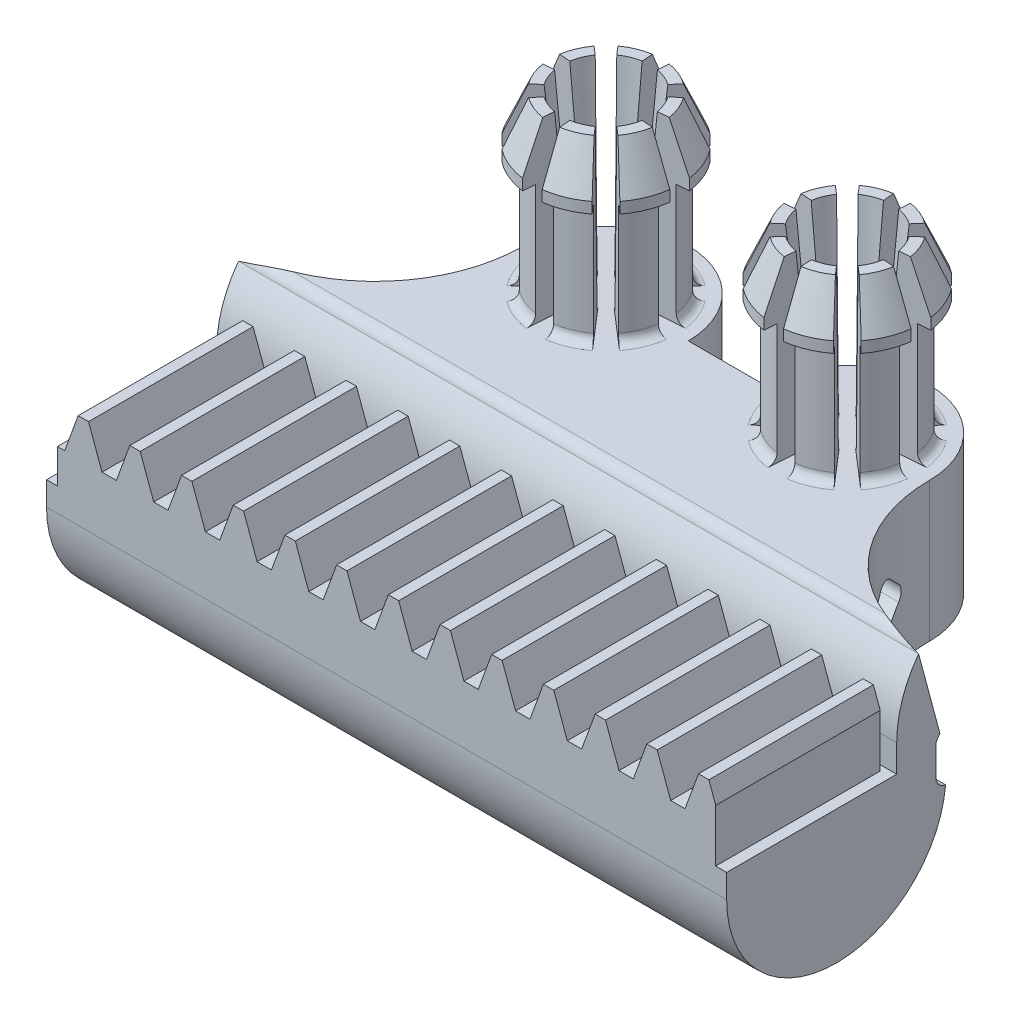
SolidWorks part; units mm, degrees
extrude "Blank" add sketch "BlankSke" against normal blind 10
sketch "BlankSke" plane through (0, 0, 0) normal (0, 0, 1) x (1, 0, 0)
  line L1 (0, 0) -> (60, 0)
  line L2 (0, 0) -> (0, 6.5)
  line L3 (0, 6.5) -> (60, 6.5)
  line L4 (60, 0) -> (60, 6.5)
  dimension "Length" = 60
ref_plane "Plane1" through (0, 0, 0) normal (0, 0, 1) x (1, 0, 0)
ref_plane "Plane2" through (0, 0, 0) normal (0, 1, 0) x (1, 0, 0)
ref_plane "Plane3" through (0, 0, 0) normal (1, 0, 0) x (0, 0, -1)
other "Configuration Table"
sketch "HoldingSke" plane through (0, 0, 0) normal (0, 1, 0) x (1, 0, 0)
  line L0 (0, 0) -> (0.0928, 0.6602)
  line L1 (-15, 0) -> (100, 0) construction
  line L2 (0, 0) -> (-2.1039, 2.3779)
  line L3 (0, 0) -> (-11.863, 4.5341)
  line L4 (0, 0) -> (8.3795, 2.0892)
  line L5 (0, 0) -> (-23.7986, -8.8762)
  line L6 (0, 0) -> (-10.5278, -7.1032)
  line L9 (-71.009, 38.7566) -> (-14.6274, 59.2778)
  line L10 (-76.2, 3.8779) -> (-71.2, 3.8779)
  line L11 (0, 0) -> (-10, 0)
  line L12 (-76.2, 101.6) -> (-76.147, 101.6)
  line L13 (24.9733, 27.94) -> (52.9518, 28.4284)
  line L14 (24.9733, 27.94) -> (24.9743, 27.94)
  line L15 (24.9733, 27.94) -> (100.4006, 29.5858)
  circle A0 centre (0, 0) radius 19.05
  circle A1 centre (0, 0) radius 2.5
  circle A2 centre (0, 0) radius 12.7
  dimension "Num_teeth" = 14
  dimension "Width" = 10
  dimension "Length" = 60
  dimension "Pitch_height" = 5
sketch "TooCutSkeIll" plane through (0, 0, 0) normal (0, 0, 1) x (1, 0, 0)
  line L0 (-1.8687, 6.4605) -> (-0.7447, 3.3724)
  line L1 (-0.3914, 3.125) -> (0.3914, 3.125)
  line L2 (0.7447, 3.3724) -> (1.8687, 6.4605)
  line L3 (60, 6.5) -> (0, 6.5) construction
  line L4 (0, 0) -> (0, 64.897) construction
  line L5 (-13.208, 5) -> (12.954, 5) construction
  line L6 (0, 0) -> (60, 0) construction
  line L7 (1.3371, 5) -> (1.3371, 48.7463) construction
  line L8 (-1.3371, 5) -> (-1.3371, 48.7463) construction
  line L9 (1.9251, 6.5) -> (1.9251, 6.5254)
  line L10 (-1.9251, 6.5) -> (-1.9251, 6.5254)
  line L11 (-1.9251, 6.5254) -> (1.9251, 6.5254)
  arc A0 (0.3914, 3.125) -> (0.7447, 3.3724) centre (0.3914, 3.501) ccw
  arc A1 (-0.7447, 3.3724) -> (-0.3914, 3.125) centre (-0.3914, 3.501) ccw
  arc A2 (1.9251, 6.5) -> (1.8687, 6.4605) centre (1.9251, 6.44) ccw
  arc A3 (-1.8687, 6.4605) -> (-1.9251, 6.5) centre (-1.9251, 6.44) ccw
  dimension "Addendum_plus" = 1.5254
  dimension "Pitch_height" = 5
  dimension "Pressure_angle" = 20
  dimension "Gap_width" = 2.6742
  dimension "Dedendum" = 1.875
extrude "ToothCutIll" [suppressed] cut sketch "TooCutSkeIll" against normal through all
sketch "TooCutSkeSim" plane through (0, 0, 0) normal (0, 0, 1) x (1, 0, 0)
  line L0 (0.6547, 3.125) -> (-0.6547, 3.125)
  line L1 (1.8923, 6.5254) -> (0.6547, 3.125)
  line L2 (0, 17.4625) -> (0, 53.467) construction
  line L3 (1.8923, 6.5254) -> (-1.8923, 6.5254)
  line L6 (-1.8923, 6.5254) -> (-0.6547, 3.125)
  line L9 (-1.3371, 5) -> (1.3371, 5) construction
  line L10 (0, 0) -> (60, 0) construction
  line L11 (1.3371, 5) -> (1.3371, 53.467) construction
  line L12 (-1.3371, 5) -> (-1.3371, 53.467) construction
  dimension "Addendum_plus" = 1.5254
  dimension "Pitch_height" = 5
  dimension "Pressure_angle" = 20
  dimension "Gap_width" = 2.6742
  dimension "Dedendum" = 1.875
extrude "ToothCutSim" cut sketch "TooCutSkeSim" against normal through all
pattern_linear "TeethCuts" count 14 spacing 4.7124 along (1, 0, 0) of "ToothCutIll", "ToothCutSim"
sketch "Sketch1" plane through (60, 0, 0) normal (1, 0, 0) x (0, 0, -1)
  line L0 (0, 0) -> (0, -10.8205)
  line L2 (10.5, 0) -> (10.5, 8.5)
  line L4 (10, 6.5) -> (0, 6.5) construction
  line L5 (10, 0) -> (10, 4.7911) construction
  line L6 (10.5, 8.5) -> (12.5, 8.5)
  line L7 (12.5, 8.5) -> (14.6603, 0.4239)
  line L8 (10.5, 0) -> (0, 0)
  arc A0 (0, -10.8205) -> (14.6603, 0.4239) centre (5, -2.1603) ccw
  dimension "D1" = 20
  dimension "D2" = 2
  dimension "D3" = 0.5
  dimension "D4" = 2
extrude "Boss-Extrude1" add sketch "Sketch1" against normal offset from surface 1 and the other way blind 1 up to face at (0, 1.5625, -5) offset beyond the face yes
sketch "Sketch2" plane through (0, 6.5, 0) normal (0, 1, 0) x (1, 0, 0)
  line L0 (30, 12.5) -> (30, 49.3305) construction
  line L1 (61, 12.5) -> (-1, 12.5) construction
  line L3 (0, 5) -> (64.3113, 5) construction
  line L4 (0, 10) -> (0, 0) construction
  circle A0 centre (19, 26) radius 7.5
  circle A1 centre (41, 26) radius 7.5
  dimension "D2" = 15
  dimension "D3" = 21
  dimension "D1" = 11
extrude "Boss-Extrude2" add sketch "Sketch2" along normal blind 2.71 and the other way blind 10 separate body
sketch "Sketch3" plane through (0, 9.21, 0) normal (0, 1, 0) x (1, 0, 0)
  line L0 (61, 15) -> (-1, 15) construction
  line L1 (11.5, 26) -> (19, 26) construction
  line L2 (30, 15) -> (30, 40.8387) construction
  line L3 (33.5, 26) -> (26.5, 26)
  line L9 (-1, 12.5) -> (61, 12.5)
  arc A0 (11.5, 26) -> (-1, 12.5) centre (-2.04, 26) cw
  circle A1 centre (19, 26) radius 7.5 construction
  arc A2 (48.5, 26) -> (61, 12.5) centre (62.04, 26) ccw
  circle A3 centre (41, 26) radius 7.5 construction
  arc A4 (33.5, 26) -> (48.5, 26) centre (41, 26) ccw
  arc A5 (11.5, 26) -> (26.5, 26) centre (19, 26) ccw
extrude "Boss-Extrude3" add sketch "Sketch3" against normal up to surface (12.71 mm away) up to face at (41, -3.5, -33.5)
ref_plane "Plane4" through (19, 0, 0) normal (-1, 0, 0) x (0, 0, 1)
sketch "Sketch4" plane through (19, 0, 0) normal (-1, 0, 0) x (0, 0, 1)
  line L0 (-26, 9.21) -> (-26, 22.6964) construction
  line L1 (-12.5, 9.21) -> (-26, 9.21) construction
  line L2 (-5, -2.1603) -> (-5, -16.7144) construction
  line L3 (-31.65, 9.21) -> (-31.65, 20.21)
  line L4 (-31.65, 20.21) -> (-32.77, 20.21)
  line L5 (-32.77, 20.21) -> (-32.77, 21.21)
  line L6 (-32.77, 21.21) -> (-31.05, 25.21)
  line L7 (-31.05, 25.21) -> (-30.05, 25.21)
  line L8 (-30.05, 25.21) -> (-28.45, 9.21)
  line L9 (-28.45, 9.21) -> (-31.65, 9.21)
  dimension "D1" = 21
  dimension "D2" = 5.65
  dimension "D3" = 1.6
  dimension "D4" = 3.2
  dimension "D5" = 11
  dimension "D6" = 1
  dimension "D7" = 4
  dimension "D8" = 1
  dimension "D9" = 1.12
revolve "Revolve1" add sketch "Sketch4" angle 360 about L0
sketch "Sketch5" plane through (0, 9.21, 0) normal (0, 1, 0) x (1, 0, 0)
  line L0 (25.77, 14.1893) -> (25.77, 24.6702) construction
  line L1 (25.77, 26) -> (19, 26) construction
  line L2 (19, 26.4) -> (25.77, 26.9)
  line L3 (19, 25.6) -> (25.77, 25.1)
  line L4 (19, 26.4) -> (19, 25.6)
  line L5 (25.77, 26.9) -> (25.77, 25.1)
  circle A1 centre (19, 26) radius 6.77 construction
  dimension "D1" = 0.8
  dimension "D2" = 1.8
extrude "Cut-Extrude1" cut sketch "Sketch5" along normal up to next
ref_axis "Axis1" through (19, 25.21, -26) along (0, -1, 0)
pattern_circular "CirPattern1" count 8 over 360 about axis through (19, 25.21, -26) along (0, -1, 0) of "Cut-Extrude1"
ref_plane "Plane5" through (30, 0, 0) normal (-1, 0, 0) x (0, 0, 1)
fillet "Fillet1" radius 0.8 16 edges at (18.0624, 9.21, -28.2635) (16.7365, 9.21, -26.9376) (16.7365, 9.21, -25.0624) (18.0624, 9.21, -23.7365) (19.9376, 9.21, -23.7365) (21.2635, 9.21, -25.0624) (21.2635, 9.21, -26.9376) (19.9376, 9.21, -28.2635) (13.7801, 9.21, -28.1622) (16.8378, 9.21, -31.2199) (21.1622, 9.21, -31.2199) (24.2199, 9.21, -28.1622) (24.2199, 9.21, -23.8378) (21.1622, 9.21, -20.7801) (13.7801, 9.21, -23.8378) (16.8378, 9.21, -20.7801)
mirror "Mirror2" about plane through (30, 0, 0) normal (-1, 0, 0) of "CirPattern1", "Cut-Extrude1", "Revolve1", "Fillet1"
sketch "Sketch6" plane through (-1, 0, 0) normal (-1, 0, 0) x (0, 0, 1)
  line L0 (-23, 9.21) -> (-23, -3.5) construction
  line L1 (-12.5, 9.21) -> (-26, 9.21) construction
  line L2 (-26, -3.5) -> (-14.9098, -3.5) construction
  line L3 (-24, -3.5) -> (-21.6665, -1.1665)
  line L4 (-21.6665, 0.2477) -> (-22.7979, 1.379)
  line L5 (-22.7979, 2.7933) -> (-21.6665, 3.9246)
  line L6 (-20.2523, 3.9246) -> (-18.0704, 1.7426)
  line L7 (-18.0704, -3.3686) -> (-18.2017, -3.5)
  line L8 (-18.2017, -3.5) -> (-24, -3.5)
  line L9 (-17.3632, 1.4497) -> (-15.0775, 1.4497)
  line L10 (-17.3632, -3.0757) -> (-15.0775, -3.0757)
  line L11 (-14.0775, 0.4497) -> (-14.0775, -2.0757)
  arc A0 (-14.6603, 0.4239) -> (0, -10.8205) centre (-5, -2.1603) ccw construction
  arc A1 (-15.0775, -3.0757) -> (-14.0775, -2.0757) centre (-15.0775, -2.0757) ccw
  arc A2 (-15.0775, 1.4497) -> (-14.0775, 0.4497) centre (-15.0775, 0.4497) cw
  arc A3 (-17.3632, 1.4497) -> (-18.0704, 1.7426) centre (-17.3632, 2.4497) cw
  arc A4 (-17.3632, -3.0757) -> (-18.0704, -3.3686) centre (-17.3632, -4.0757) ccw
  arc A5 (-21.6665, -1.1665) -> (-21.6665, 0.2477) centre (-22.3737, -0.4594) ccw
  arc A6 (-22.7979, 1.379) -> (-22.7979, 2.7933) centre (-22.0908, 2.0861) cw
  arc A7 (-21.6665, 3.9246) -> (-20.2523, 3.9246) centre (-20.9594, 3.2175) cw
  point P22 (-14.0775, -3.0757)
  point P27 (-17.7775, 1.4497)
  point P30 (-17.7775, -3.0757)
  point P33 (-20.9594, -0.4594)
  point P36 (-23.505, 2.0861)
  point P39 (-20.9594, 4.6317)
  dimension "D10" = 1
  dimension "D1" = 18
  dimension "D2" = 45
  dimension "D3" = 4.1
  dimension "D4" = 3.6
  dimension "D5" = 4.3
  dimension "D6" = 3.6
  dimension "D7" = 1
  dimension "D8" = 4.5
  dimension "D9" = 3.7
extrude "Cut-Extrude2" cut sketch "Sketch6" against normal up to next
fillet "Fillet2" radius 8 1 edges at (30, -3.5, -14.9098)
sketch "Sketch7" plane through (0, 0, 0) normal (0, 0, 1) x (1, 0, 0)
  line L59 (60, 0) -> (60, 4.7911)
  line L60 (60, 4.7911) -> (59.378, 6.5)
  line L61 (59.378, 6.5) -> (58.4317, 6.5)
  line L62 (58.4317, 6.5) -> (57.2033, 3.125)
  line L63 (57.2033, 3.125) -> (55.894, 3.125)
  line L64 (55.894, 3.125) -> (54.6656, 6.5)
  line L65 (54.6656, 6.5) -> (53.7193, 6.5)
  line L66 (53.7193, 6.5) -> (52.4909, 3.125)
  line L67 (52.4909, 3.125) -> (51.1816, 3.125)
  line L68 (51.1816, 3.125) -> (49.9532, 6.5)
  line L69 (49.9532, 6.5) -> (49.0069, 6.5)
  line L70 (49.0069, 6.5) -> (47.7785, 3.125)
  line L71 (47.7785, 3.125) -> (46.4692, 3.125)
  line L72 (46.4692, 3.125) -> (45.2408, 6.5)
  line L73 (45.2408, 6.5) -> (44.2946, 6.5)
  line L74 (44.2946, 6.5) -> (43.0662, 3.125)
  line L75 (43.0662, 3.125) -> (41.7568, 3.125)
  line L76 (41.7568, 3.125) -> (40.5284, 6.5)
  line L77 (40.5284, 6.5) -> (39.5822, 6.5)
  line L78 (39.5822, 6.5) -> (38.3538, 3.125)
  line L79 (38.3538, 3.125) -> (37.0445, 3.125)
  line L80 (37.0445, 3.125) -> (35.8161, 6.5)
  line L81 (35.8161, 6.5) -> (34.8698, 6.5)
  line L82 (34.8698, 6.5) -> (33.6414, 3.125)
  line L83 (33.6414, 3.125) -> (32.3321, 3.125)
  line L84 (32.3321, 3.125) -> (31.1037, 6.5)
  line L85 (31.1037, 6.5) -> (30.1574, 6.5)
  line L86 (30.1574, 6.5) -> (28.929, 3.125)
  line L87 (28.929, 3.125) -> (27.6197, 3.125)
  line L88 (27.6197, 3.125) -> (26.3913, 6.5)
  line L89 (26.3913, 6.5) -> (25.445, 6.5)
  line L90 (25.445, 6.5) -> (24.2166, 3.125)
  line L91 (24.2166, 3.125) -> (22.9073, 3.125)
  line L92 (22.9073, 3.125) -> (21.6789, 6.5)
  line L93 (21.6789, 6.5) -> (20.7326, 6.5)
  line L94 (20.7326, 6.5) -> (19.5042, 3.125)
  line L95 (19.5042, 3.125) -> (18.1949, 3.125)
  line L96 (18.1949, 3.125) -> (16.9665, 6.5)
  line L97 (16.9665, 6.5) -> (16.0202, 6.5)
  line L98 (16.0202, 6.5) -> (14.7918, 3.125)
  line L99 (14.7918, 3.125) -> (13.4825, 3.125)
  line L100 (13.4825, 3.125) -> (12.2541, 6.5)
  line L101 (12.2541, 6.5) -> (11.3078, 6.5)
  line L102 (11.3078, 6.5) -> (10.0794, 3.125)
  line L103 (10.0794, 3.125) -> (8.7701, 3.125)
  line L104 (8.7701, 3.125) -> (7.5417, 6.5)
  line L105 (7.5417, 6.5) -> (6.5954, 6.5)
  line L106 (6.5954, 6.5) -> (5.367, 3.125)
  line L107 (5.367, 3.125) -> (4.0577, 3.125)
  line L108 (4.0577, 3.125) -> (2.8293, 6.5)
  line L109 (2.8293, 6.5) -> (1.8831, 6.5)
  line L110 (1.8831, 6.5) -> (0.6547, 3.125)
  line L111 (0.6547, 3.125) -> (0, 3.125)
  line L112 (0, 3.125) -> (0, 0)
  line L113 (0, 0) -> (-1, 0)
  line L114 (-1, 0) -> (-1, -10.8205)
  line L115 (-1, -10.8205) -> (61, -10.8205)
  line L116 (61, -10.8205) -> (61, 0)
  line L117 (61, 0) -> (60, 0)
  line L118 (60, 0) -> (60, 4.7911)
  line L119 (60, 4.7911) -> (59.378, 6.5)
  line L120 (59.378, 6.5) -> (58.4317, 6.5)
  line L121 (58.4317, 6.5) -> (57.2033, 3.125)
  line L122 (57.2033, 3.125) -> (55.894, 3.125)
  line L123 (55.894, 3.125) -> (54.6656, 6.5)
  line L124 (54.6656, 6.5) -> (53.7193, 6.5)
  line L125 (53.7193, 6.5) -> (52.4909, 3.125)
  line L126 (52.4909, 3.125) -> (51.1816, 3.125)
  line L127 (51.1816, 3.125) -> (49.9532, 6.5)
  line L128 (49.9532, 6.5) -> (49.0069, 6.5)
  line L129 (49.0069, 6.5) -> (47.7785, 3.125)
  line L130 (47.7785, 3.125) -> (46.4692, 3.125)
  line L131 (46.4692, 3.125) -> (45.2408, 6.5)
  line L132 (45.2408, 6.5) -> (44.2946, 6.5)
  line L133 (44.2946, 6.5) -> (43.0662, 3.125)
  line L134 (43.0662, 3.125) -> (41.7568, 3.125)
  line L135 (41.7568, 3.125) -> (40.5284, 6.5)
  line L136 (40.5284, 6.5) -> (39.5822, 6.5)
  line L137 (39.5822, 6.5) -> (38.3538, 3.125)
  line L138 (38.3538, 3.125) -> (37.0445, 3.125)
  line L139 (37.0445, 3.125) -> (35.8161, 6.5)
  line L140 (35.8161, 6.5) -> (34.8698, 6.5)
  line L141 (34.8698, 6.5) -> (33.6414, 3.125)
  line L142 (33.6414, 3.125) -> (32.3321, 3.125)
  line L143 (32.3321, 3.125) -> (31.1037, 6.5)
  line L144 (31.1037, 6.5) -> (30.1574, 6.5)
  line L145 (30.1574, 6.5) -> (28.929, 3.125)
  line L146 (28.929, 3.125) -> (27.6197, 3.125)
  line L147 (27.6197, 3.125) -> (26.3913, 6.5)
  line L148 (26.3913, 6.5) -> (25.445, 6.5)
  line L149 (25.445, 6.5) -> (24.2166, 3.125)
  line L150 (24.2166, 3.125) -> (22.9073, 3.125)
  line L151 (22.9073, 3.125) -> (21.6789, 6.5)
  line L152 (21.6789, 6.5) -> (20.7326, 6.5)
  line L153 (20.7326, 6.5) -> (19.5042, 3.125)
  line L154 (19.5042, 3.125) -> (18.1949, 3.125)
  line L155 (18.1949, 3.125) -> (16.9665, 6.5)
  line L156 (16.9665, 6.5) -> (16.0202, 6.5)
  line L157 (16.0202, 6.5) -> (14.7918, 3.125)
  line L158 (14.7918, 3.125) -> (13.4825, 3.125)
  line L159 (13.4825, 3.125) -> (12.2541, 6.5)
  line L160 (12.2541, 6.5) -> (11.3078, 6.5)
  line L161 (11.3078, 6.5) -> (10.0794, 3.125)
  line L162 (10.0794, 3.125) -> (8.7701, 3.125)
  line L163 (8.7701, 3.125) -> (7.5417, 6.5)
  line L164 (7.5417, 6.5) -> (6.5954, 6.5)
  line L165 (6.5954, 6.5) -> (5.367, 3.125)
  line L166 (5.367, 3.125) -> (4.0577, 3.125)
  line L167 (4.0577, 3.125) -> (2.8293, 6.5)
  line L168 (2.8293, 6.5) -> (1.8831, 6.5)
  line L169 (1.8831, 6.5) -> (0.6547, 3.125)
  line L170 (0.6547, 3.125) -> (0, 3.125)
  line L171 (0, 3.125) -> (0, 0)
  line L172 (0, 0) -> (-1, 0)
  line L173 (-1, 0) -> (-1, -10.8205)
  line L174 (-1, -10.8205) -> (61, -10.8205)
  line L175 (61, -10.8205) -> (61, 0)
  line L176 (61, 0) -> (60, 0)
  dimension "D1" = 0
extrude "Boss-Extrude4" add sketch "Sketch7" along normal blind 5
sketch "Sketch8" plane through (-1, 0, 0) normal (-1, 0, 0) x (0, 0, 1)
  line L0 (5, -2.1603) -> (5, -12.1603)
  line L1 (5, -12.1603) -> (-5, -12.1603)
  arc A0 (-5, -12.1603) -> (5, -2.1603) centre (-5, -2.1603) ccw
  arc A1 (-14.9587, -3.0687) -> (0, -10.8205) centre (-5, -2.1603) ccw construction
extrude "Cut-Extrude3" cut sketch "Sketch8" against normal up to next
sketch "Sketch9" plane through (0, 9.21, 0) normal (0, 1, 0) x (1, 0, 0)
  line L0 (30, 26) -> (30, -5)
  line L1 (33.5, 26) -> (26.5, 26) construction
  line L2 (30.1574, -5) -> (28.929, -5) construction
fillet "Fillet3" radius 10 1 edges at (30, 8.5, -10.5)
fillet "Fillet4" radius 1 1 edges at (30, 9.21, -12.5)
equation "' \"Module@HoldingSke\" = 6.35"
equation "' \"Num_teeth@HoldingSke\" = 12"
equation "' \"Ap@HoldingSke\" =  20"
equation "' \"Ap@HoldingSke\" = 20"
equation "' \"Width@HoldingSke\" = 0.25 * 25.4"
equation "' \"Show_teeth@HoldingSke\" = 500"
equation "' \"Backlash@HoldingSke\" = 0.009 * 25.4"
equation "' \"Addendum_fac@HoldingSke\" = 1.0"
equation "' \"Dedendum_fac@HoldingSke\" = 1.25"
equation "' \"Dedendum_add@HoldingSke\" = 0.00005 * 25.4"
equation "' \"Clearance_fac@HoldingSke\" = 0.25"
equation "' \"Pitch_height@HoldingSke\" = 1 * 25.4"
equation "' \"Length@HoldingSke\" = 4.71 * 25.4"
equation "\"Pitch@HoldingSke\" = 1 / \"Module@HoldingSke\""
equation "\"MPH@HoldingSke\" = \"Dedendum_fac@HoldingSke\" / \"Pitch@HoldingSke\" + 2 * \"Dedendum_add@HoldingSke\" + 0.002 * 25.4"
equation "\"MPH@HoldingSke\" = ((sgn( \"MPH@HoldingSke\" - \"Pitch_height@HoldingSke\")+1)*( \"MPH@HoldingSke\" - \"Pitch_height@HoldingSke\"))/2 + \"Pitch_height@HoldingSke\""
equation "\"Blank_height@BlankSke\" = \"Pitch_height@HoldingSke\" + \"Addendum_fac@HoldingSke\"  / \"Pitch@HoldingSke\" "
equation "\"Length@BlankSke\" =  \"Length@HoldingSke\""
equation "\"Face_width@Blank\" = \"Width@HoldingSke\""
equation "\"Pressure_angle@TooCutSkeIll\" = \"Ap@HoldingSke\""
equation "\"Addendum_plus@TooCutSkeIll\" =  \"Addendum_fac@HoldingSke\"  / \"Pitch@HoldingSke\" + 0.001 *25.4"
equation "\"Dedendum@TooCutSkeIll\" = \"Dedendum_fac@HoldingSke\"  / \"Pitch@HoldingSke\""
equation "\"Pitch_height@TooCutSkeIll\" =  \"MPH@HoldingSke\""
equation "\"Gap_width@TooCutSkeIll\" = 3.14159265 / 2 / \"Pitch@HoldingSke\" + 6 * \"Backlash@HoldingSke\""
equation "\"Pressure_angle@TooCutSkeSim\" = \"Ap@HoldingSke\""
equation "\"Addendum_plus@TooCutSkeSim\" =  \"Addendum_fac@HoldingSke\"  / \"Pitch@HoldingSke\" + 0.001 * 25.4"
equation "\"Dedendum@TooCutSkeSim\" = \"Dedendum_fac@HoldingSke\"  / \"Pitch@HoldingSke\""
equation "\"Pitch_height@TooCutSkeSim\" =  \"MPH@HoldingSke\""
equation "\"Gap_width@TooCutSkeSim\" = 3.14159265 / 2 / \"Pitch@HoldingSke\" + 6 * \"Backlash@HoldingSke\""
equation "\"Root_fillet@TooCutSkeIll\" = \"Clearance_fac@HoldingSke\" / \"Pitch@HoldingSke\" + \"Dedendum_add@HoldingSke\""
equation "\"Break_rad@TooCutSkeIll\" = 0.02 / \"Pitch@HoldingSke\" * 2"
equation "\"Linear_pitch@TeethCuts\" = 3.14159265 / \"Pitch@HoldingSke\""
equation "\"Num_teeth@HoldingSke\" = int( ( \"Length@HoldingSke\" + 0 ) / (3.14159265 / \"Pitch@HoldingSke\")) + 0.9999  + 1"
equation " \"Num_teeth@TeethCuts\" = int( \"Show_teeth@HoldingSke\" ) + 1"
equation " \"Num_teeth@TeethCuts\" = ((sgn( \"Num_teeth@TeethCuts\" - \"Num_teeth@HoldingSke\" )-1)*( \"Num_teeth@TeethCuts\" - \"Num_teeth@HoldingSke\" ))/-2+ \"Num_teeth@HoldingSke\""
equation " \"Num_teeth@TeethCuts\" = ((sgn( \"Num_teeth@TeethCuts\" - 2.0)+1)*( \"Num_teeth@TeethCuts\" - 2.0))/2 +2.0"
